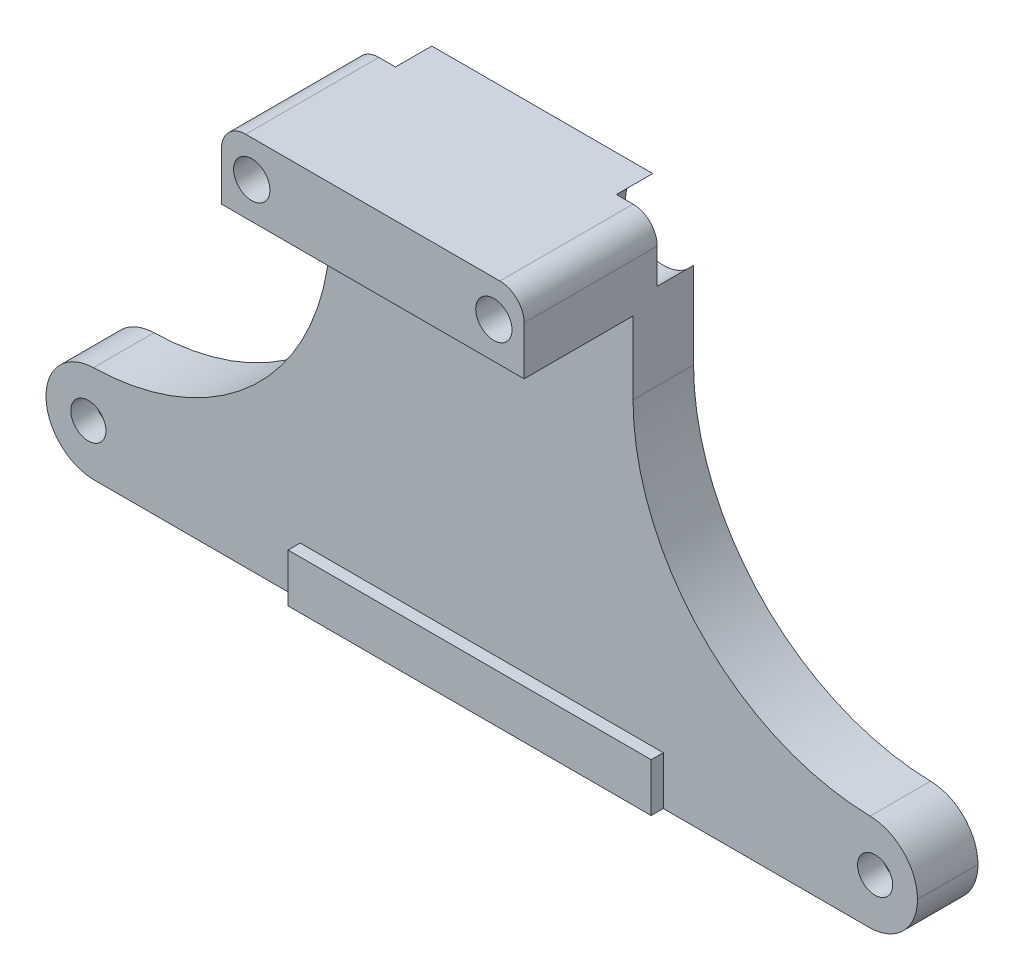
SolidWorks part; units mm, degrees
ref_plane "Спереди" through (0, 0, 0) normal (0, 0, 1) x (1, 0, 0)
ref_plane "Сверху" through (0, 0, 0) normal (0, 1, 0) x (1, 0, 0)
ref_plane "Справа" through (0, 0, 0) normal (1, 0, 0) x (0, 0, -1)
sketch "Эскиз1" plane through (0, 0, 0) normal (0, 0, 1) x (1, 0, 0)
  line L0 (-1000, 0) -> (49000, 0) construction
  line L1 (-36, -4) -> (36, -4)
  line L2 (-36, -4) -> (-36, 4)
  line L3 (-36, 4) -> (36, 4)
  line L4 (36, -4) -> (36, 4)
  line L5 (-36, -4) -> (36, 4) construction
  line L6 (-36, 4) -> (36, -4) construction
  circle A0 centre (-32.5, 0) radius 1.45
  circle A1 centre (32.5, 0) radius 1.45
  point P0 (0, 0)
  dimension "D2" = 2.9
  dimension "D1" = 8
  dimension "D3" = 65
  dimension "D4" = 32.5
  dimension "D5" = 72
extrude "Бобышка-Вытянуть1" add sketch "Эскиз1" along normal blind 5
sketch "Эскиз2" plane through (0, 0, 0) normal (0, 0, -1) x (-1, 0, 0)
  line L0 (-36, 4) -> (36, 4) construction
  line L1 (-12.5, 4) -> (12.5, 4)
  line L2 (-12.5, 4) -> (-12.5, 36)
  line L3 (-12.5, 36) -> (12.5, 36)
  line L4 (12.5, 4) -> (12.5, 36)
  line L5 (-12.5, 4) -> (12.5, 36) construction
  line L6 (-12.5, 36) -> (12.5, 4) construction
  line L7 (-1006.5256, 33) -> (48993.4744, 33) construction
  line L8 (0, -1000) -> (0, 49000) construction
  circle A0 centre (-10, 33) radius 1.5
  circle A1 centre (10, 33) radius 1.5
  point P4 (0, 20)
  dimension "D1" = 20
  dimension "D3" = 3
  dimension "D2" = 10
  dimension "D4" = 25
  dimension "D5" = 3
  dimension "D6" = 32
extrude "Бобышка-Вытянуть2" add sketch "Эскиз2" against normal blind 5
sketch "Эскиз3" plane through (0, 0, 5) normal (0, 0, -1) x (-1, 0, 0)
  line L0 (12.5, 4) -> (12.5, 36) construction
  line L1 (-12.5, 36) -> (12.5, 36)
  line L2 (-12.5, 36) -> (-12.5, 30)
  line L3 (-12.5, 30) -> (12.5, 30)
  line L4 (12.5, 36) -> (12.5, 30)
  line L5 (-12.5, 36) -> (12.5, 30) construction
  line L6 (-12.5, 30) -> (12.5, 36) construction
  circle A0 centre (10, 33) radius 1.5 construction
  circle A1 centre (-10, 33) radius 1.5 construction
  circle A2 centre (10, 33) radius 1.5
  circle A3 centre (-10, 33) radius 1.5
  point P4 (0, 33)
  dimension "D1" = 6
extrude "Бобышка-Вытянуть3" add sketch "Эскиз3" against normal blind 9
fillet "Скругление1" radius 20 2 edges at (12.5, 4, 2.5) (-12.5, 4, 2.5)
fillet "Скругление2" radius 4 4 edges at (-36, -4, 2.5) (-36, 4, 2.5) (36, -4, 2.5) (36, 4, 2.5)
fillet "Скругление3" radius 2 2 edges at (12.5, 36, 7) (-12.5, 36, 7)
sketch "Эскиз4" plane through (0, 0, 0) normal (0, 0, -1) x (-1, 0, 0)
  circle A0 centre (-10, 33) radius 3.125
  circle A1 centre (10, 33) radius 3.125
  circle A2 centre (-32.5, 0) radius 3.125
  circle A3 centre (32.5, 0) radius 3.125
  dimension "D1" = 6.25
extrude "Вырез-Вытянуть3" cut sketch "Эскиз4" against normal blind 3
sketch "Эскиз5" plane through (0, 0, 5) normal (0, 0, 1) x (1, 0, 0)
  line L0 (-32, -4) -> (32, -4) construction
  line L1 (15, -4) -> (-15, -4)
  line L2 (15, -4) -> (15, 0)
  line L3 (15, 0) -> (-15, 0)
  line L4 (-15, -4) -> (-15, 0)
  line L5 (15, -4) -> (-15, 0) construction
  line L6 (15, 0) -> (-15, -4) construction
  line L7 (12.5, 30) -> (12.5, 24) construction
  line L8 (-12.5, 24) -> (-12.5, 30) construction
  point P4 (0, -2)
  dimension "D1" = 2.5
  dimension "D2" = 2.5
  dimension "D3" = 4
extrude "Бобышка-Вытянуть4" add sketch "Эскиз5" along normal blind 1
